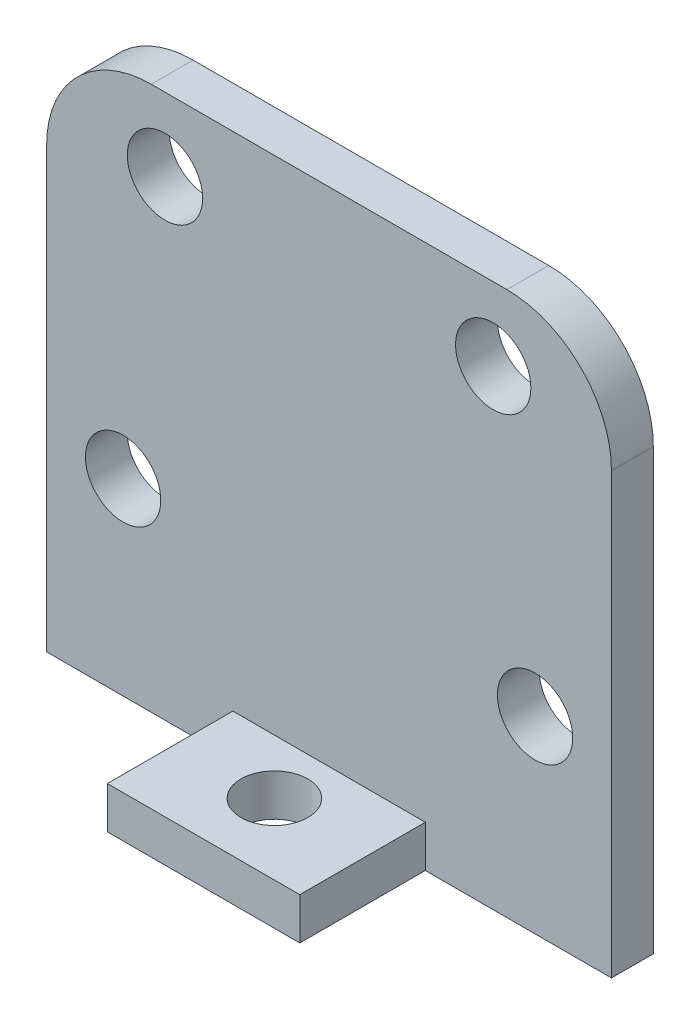
SolidWorks part; units mm, degrees
ref_plane "Front" through (0, 0, 0) normal (0, 0, 1) x (1, 0, 0)
ref_plane "Top" through (0, 0, 0) normal (0, 1, 0) x (1, 0, 0)
ref_plane "Right" through (0, 0, 0) normal (1, 0, 0) x (0, 0, -1)
sketch "Sketch1" plane through (0, 0, 0) normal (0, 0, 1) x (1, 0, 0)
  line L0 (13.5, 21) -> (13.5, 0) construction
  line L1 (-13.5, 26) -> (13.5, 26)
  line L2 (-13.5, 26) -> (-13.5, 0)
  line L3 (-13.5, 0) -> (13.5, 0)
  line L4 (13.5, 26) -> (13.5, 0)
  line L5 (-8.5, 26) -> (8.5, 26) construction
extrude "Boss-Extrude1" add sketch "Sketch1" along normal blind 2
sketch "Sketch2" plane through (0, 0, 2) normal (0, 0, 1) x (1, 0, 0)
  line L0 (13.5, 0) -> (13.5, 26) construction
  line L1 (-13.5, 0) -> (13.5, 0)
  line L2 (-13.5, 0) -> (-13.5, 2)
  line L3 (-13.5, 2) -> (13.5, 2)
  line L4 (13.5, 0) -> (13.5, 2)
  dimension "D1" = 2
extrude "Boss-Extrude2" add sketch "Sketch2" along normal blind 6
sketch "Sketch3" plane through (0, 0, 0) normal (0, -1, 0) x (1, 0, 0)
  circle A0 centre (0, 4.615) radius 1.6 construction
  circle A1 centre (0, 4.615) radius 1.6
extrude "Cut-Extrude1" cut sketch "Sketch3" against normal up to next
sketch "Sketch4" plane through (0, 2, 0) normal (0, 1, 0) x (1, 0, 0)
  line L0 (13.5, -2) -> (-13.5, -2) construction
  line L1 (13.5, -8) -> (4.6, -8)
  line L2 (13.5, -8) -> (13.5, -2)
  line L3 (13.5, -2) -> (4.6, -2)
  line L4 (4.6, -8) -> (4.6, -2)
  line L5 (1.6, -8) -> (1.6, -2) construction
  line L6 (13.5, -8) -> (-13.5, -8) construction
  line L7 (13.5, -2) -> (-13.5, -2) construction
  circle A0 centre (0, -4.615) radius 1.6 construction
  dimension "D1" = 3
extrude "Cut-Extrude2" cut sketch "Sketch4" against normal up to next
mirror "Mirror1" about plane through (0, 0, 0) normal (1, 0, 0) of "Cut-Extrude2"
sketch "Sketch5" plane through (0, 0, 0) normal (0, 0, -1) x (-1, 0, 0)
  circle A0 centre (-7.8459, 22.5) radius 1.8 construction
  circle A1 centre (7.8459, 22.5) radius 1.8 construction
  circle A2 centre (-9.8466, 9) radius 1.8 construction
  circle A3 centre (9.8466, 9) radius 1.8 construction
  circle A4 centre (-7.8459, 22.5) radius 1.8
  circle A5 centre (7.8459, 22.5) radius 1.8
  circle A6 centre (-9.8466, 9) radius 1.8
  circle A7 centre (9.8466, 9) radius 1.8
extrude "Cut-Extrude3" cut sketch "Sketch5" against normal up to next
fillet "Fillet1" radius 5 2 edges at (-13.5, 26, 1) (13.5, 26, 1)
